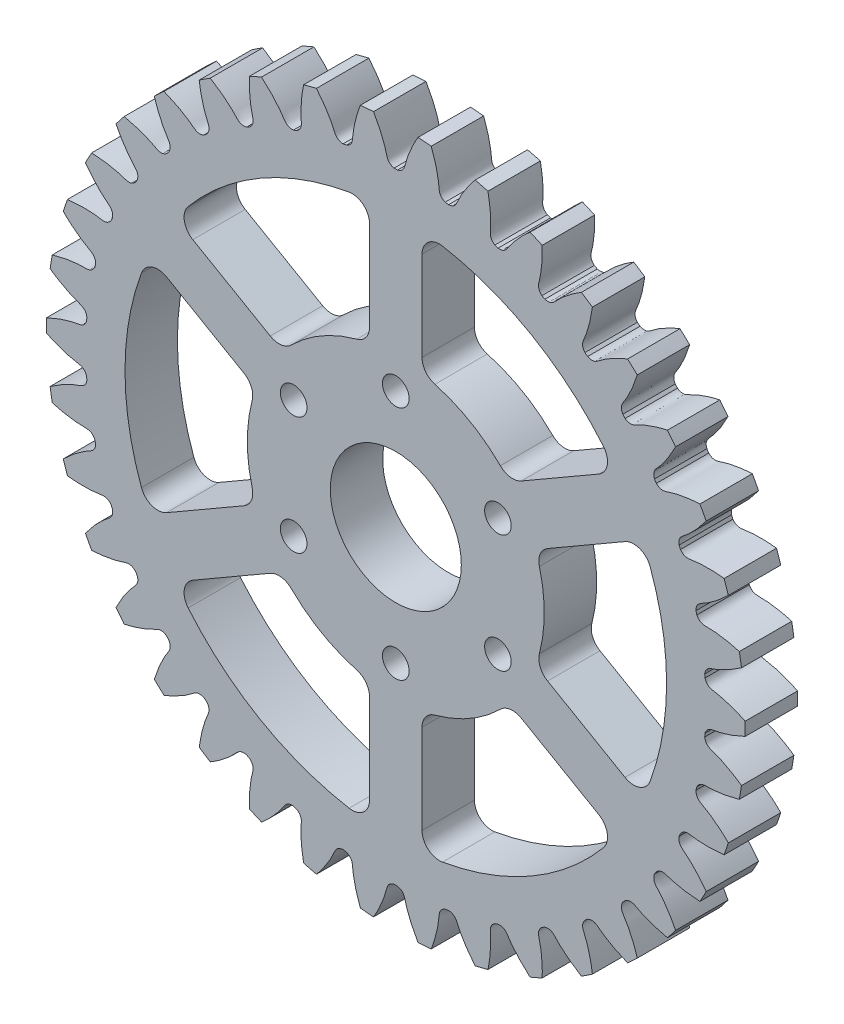
SolidWorks part; units mm, degrees
material "POM Acetal Coopolymer聚甲醛树脂"
ref_plane "前视基准面" through (0, 0, 0) normal (0, 0, 1) x (1, 0, 0)
ref_plane "上视基准面" through (0, 0, 0) normal (0, 1, 0) x (1, 0, 0)
ref_plane "右视基准面" through (0, 0, 0) normal (1, 0, 0) x (0, 0, -1)
other "Configuration Table"
sketch "草图1" plane through (0, 0, 0) normal (0, 0, 1) x (1, 0, 0)
  circle A0 centre (0, 0) radius 40
extrude "凸台-拉伸1" add sketch "草图1" along normal mid plane 6
ref_axis "基准轴1" through (0, 0, -3.3) along (0, 0, 1)
sketch "草图2" plane through (0, 0, 0) normal (0, 0, 1) x (1, 0, 0)
  line L0 (0, 0) -> (0, 40) construction
  circle A0 centre (0, 0) radius 40 construction
  arc A1 (0.1947, 35.4995) -> (-0.1947, 35.4995) centre (0, 0) ccw
  arc A2 (7.2236, 45.4878) -> (-7.2236, 45.4878) centre (0, 0) ccw
  spline S0 degree 3 poles (0.1947, 35.4995) (0.9263, 35.6731) (1.0025, 36.2353) (1.1703, 36.8342) (1.2246, 37.0153) (1.2869, 37.2088) (1.3577, 37.4145) (1.4375, 37.6322) (1.5268, 37.8616) (1.6262, 38.1023) (1.736, 38.3542) (1.8569, 38.6167) (1.9892, 38.8896) (2.1334, 39.1726) (2.2899, 39.4652) (2.4593, 39.767) (2.6419, 40.0778) (2.8382, 40.397) (3.0485, 40.7242) (3.2733, 41.059) (3.513, 41.401) (3.7679, 41.7496) (4.0383, 42.1044) (4.3247, 42.4649) (4.6273, 42.8307) (4.9465, 43.2011) (5.2826, 43.5757) (5.6358, 43.954) (6.0065, 44.3353) (6.5312, 44.8539) (6.9416, 45.2356) (7.2236, 45.4878) knots 0 0 0 0 0.121483 0.135609 0.150891 0.167327 0.184918 0.203664 0.223564 0.24462 0.26683 0.290195 0.314715 0.340389 0.367219 0.395203 0.424342 0.454635 0.486084 0.518687 0.552445 0.587358 0.623426 0.660648 0.699025 0.738557 0.779244 0.821086 0.864082 0.908233 1 1 1 1
  spline S1 degree 3 poles (-0.1947, 35.4995) (-0.9263, 35.6731) (-1.0025, 36.2353) (-1.1703, 36.8342) (-1.2246, 37.0153) (-1.2869, 37.2088) (-1.3577, 37.4145) (-1.4375, 37.6322) (-1.5268, 37.8616) (-1.6262, 38.1023) (-1.736, 38.3542) (-1.8569, 38.6167) (-1.9892, 38.8896) (-2.1334, 39.1726) (-2.2899, 39.4652) (-2.4593, 39.767) (-2.6419, 40.0778) (-2.8382, 40.397) (-3.0485, 40.7242) (-3.2733, 41.059) (-3.513, 41.401) (-3.7679, 41.7496) (-4.0383, 42.1044) (-4.3247, 42.4649) (-4.6273, 42.8307) (-4.9465, 43.2011) (-5.2826, 43.5757) (-5.6358, 43.954) (-6.0065, 44.3353) (-6.5312, 44.8539) (-6.9416, 45.2356) (-7.2236, 45.4878) knots 0 0 0 0 0.121483 0.135609 0.150891 0.167327 0.184918 0.203664 0.223564 0.24462 0.26683 0.290195 0.314715 0.340389 0.367219 0.395203 0.424342 0.454635 0.486084 0.518687 0.552445 0.587358 0.623426 0.660648 0.699025 0.738557 0.779244 0.821086 0.864082 0.908233 1 1 1 1
extrude "切除-拉伸1" cut sketch "草图2" along normal mid plane 180
pattern_circular "阵列(圆周)1" count 38 every 9.474 about axis through (0, 0, -3.3) along (0, 0, 1) of "切除-拉伸1"
sketch "草图3" plane through (0, 0, 0) normal (0, 0, 1) x (1, 0, 0)
  circle A0 centre (0, 0) radius 38 construction
  dimension "Dn" = 76
sketch "草图4" plane through (0, 0, 3) normal (0, 0, 1) x (1, 0, 0)
  circle A0 centre (0, 0) radius 13.5 construction
  circle A1 centre (0, 13.5) radius 1.525
  circle A2 centre (11.6913, 6.75) radius 1.525
  circle A3 centre (11.6913, -6.75) radius 1.525
  circle A4 centre (0, -13.5) radius 1.525
  circle A5 centre (-11.6913, -6.75) radius 1.525
  circle A6 centre (-11.6913, 6.75) radius 1.525
  point P17 (0, 0)
  dimension "D1" = 27
  dimension "D2" = 3.05
  dimension "D3" = 6
extrude "切除-拉伸2" cut sketch "草图4" against normal mid plane 40
sketch "草图5" plane through (0, 0, 3) normal (0, 0, 1) x (1, 0, 0)
  circle A0 centre (0, 0) radius 7.5
  dimension "D1" = 15
extrude "切除-拉伸3" cut sketch "草图5" against normal mid plane 40
sketch "草图6" plane through (0, 0, 3) normal (0, 0, 1) x (1, 0, 0)
  line L0 (0, 31) -> (0, -31) construction
  line L1 (26.8468, -15.5) -> (-26.8468, 15.5) construction
  line L2 (-26.8468, -15.5) -> (26.8468, 15.5) construction
  line L3 (-3, 31) -> (-3, -31)
  line L4 (28.3468, -12.9019) -> (-25.3468, 18.0981)
  line L5 (-25.3468, -18.0981) -> (28.3468, 12.9019)
  line L6 (3, 31) -> (3, -31)
  line L7 (25.3468, -18.0981) -> (-28.3468, 12.9019)
  line L8 (-28.3468, -12.9019) -> (25.3468, 18.0981)
  circle A0 centre (0, 0) radius 31
  circle A1 centre (0, 0) radius 17
  point P12 (0, 0)
  dimension "D1" = 62
  dimension "D2" = 34
  dimension "D3" = 3
  dimension "D4" = 3
  dimension "D5" = 3
extrude "切除-拉伸4" cut sketch "草图6" against normal blind 10 contours A1 L7 A0 L8 | A1 L3 A0 L4 | A1 L8 A0 L6 | A1 L4 A0 L5 | A1 L6 A0 L7 | A1 L5 A0 L3 region at (-12.1134, 20.981, 3) region at (12.1134, 20.981, 3) region at (-24.2267, 0, 3) region at (24.2267, 0, 3) region at (-12.1134, -20.981, 3) region at (12.1134, -20.981, 3)
fillet "圆角1" radius 2 24 edges at (15.9914, 5.7685, 0) (28.2208, 12.8292, 0) (28.2208, -12.8292, 0) (15.9914, -5.7685, 0) (3, 16.7332, 0) (3, 30.8545, 0) (25.2208, 18.0253, 0) (12.9914, 10.9647, 0) (-3, -16.7332, 0) (-3, -30.8545, 0) (-25.2208, -18.0253, 0) (-12.9914, -10.9647, 0) (-15.9914, -5.7685, 0) (-28.2208, -12.8292, 0) (-12.9914, 10.9647, 0) (-25.2208, 18.0253, 0) (-3, 30.8545, 0) (-3, 16.7332, 0) (12.9914, -10.9647, 0) (25.2208, -18.0253, 0) (3, -30.8545, 0) (3, -16.7332, 0) (-28.2208, 12.8292, 0) (-15.9914, 5.7685, 0)
